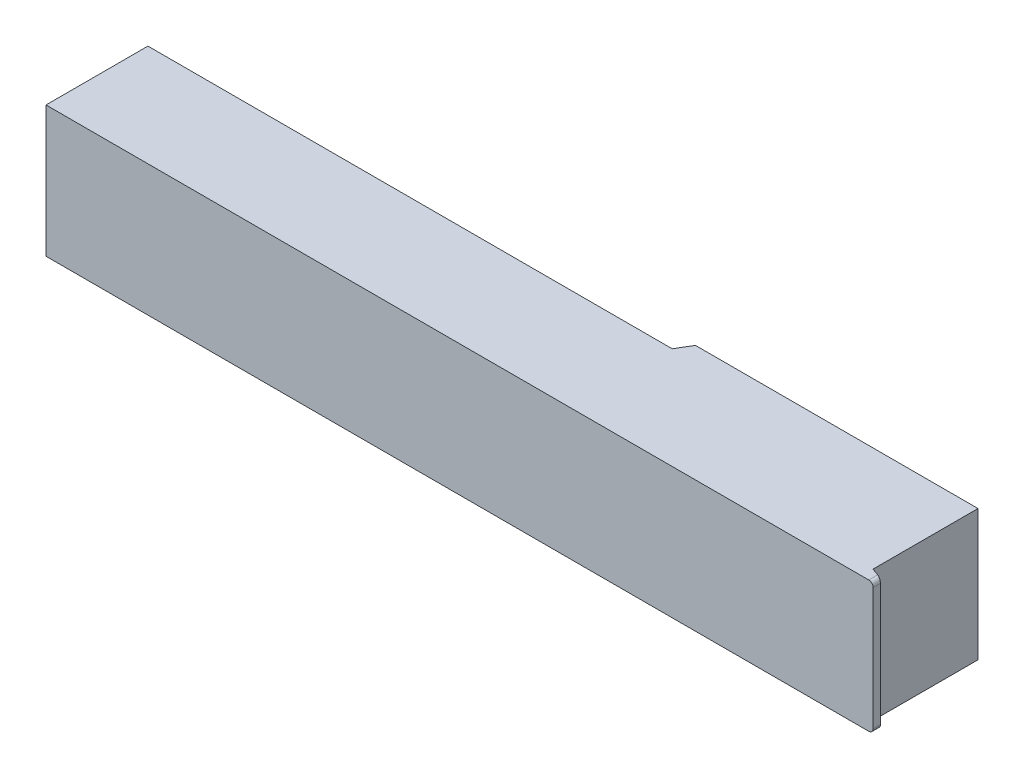
SolidWorks part; units mm, degrees
ref_plane "Front Plane" through (0, 0, 0) normal (1, 0, 0) x (0, 1, 0)
ref_plane "Top Plane" through (0, 0, 0) normal (0, 0, 1) x (0, 1, 0)
ref_plane "Right Plane" through (0, 0, 0) normal (0, 1, 0) x (-1, 0, 0)
sketch "Sketch1" plane through (0, 0, 0) normal (0, 0, 1) x (0, 1, 0)
  line L1 (0, 0) -> (22.5, 0)
  line L2 (0, 0) -> (0, -142)
  line L3 (0, -142) -> (22.5, -142)
  line L4 (22.5, 0) -> (22.5, -142)
extrude "Boss-Extrude1" add sketch "Sketch1" against normal blind 20 contours L2 L3 L4 L1
sketch "Sketch2" plane through (142, 0, 0) normal (1, 0, 0) x (0, 1, 0)
  line L0 (22.5, -20) -> (22.5, 0) construction
  line L1 (0, -20) -> (22.5, -20)
  line L2 (0, -20) -> (0, -2)
  line L3 (0, -2) -> (22.5, -2)
  line L4 (22.5, -20) -> (22.5, -2)
extrude "Cut-Extrude1" cut sketch "Sketch2" against normal blind 2 contours L3 L4 L1 L2
chamfer "Chamfer5" distance 0.75 angle 70 1 edges at (142, 11.25, -2)
fillet "Fillet5" radius 0.75 2 edges at (142, 0, -0.625) (142, 22.5, -0.625)
sketch "Sketch3" plane through (0, 22.5, 0) normal (0, 1, 0) x (-1, 0, 0)
  line L0 (0, 0) -> (-141.25, 0) construction
  line L1 (-140, -20) -> (-30, -20)
  line L2 (-140, -20) -> (-140, 0)
  line L3 (-140, 0) -> (-30, 0)
  line L4 (-30, -20) -> (-30, 0)
  line L5 (0, -20) -> (0, 0) construction
  line L6 (-30, -20) -> (0, -20)
  line L7 (-30, -20) -> (-30, -10)
  line L8 (-30, -10) -> (0, -10)
  line L9 (0, -20) -> (0, -10)
  line L11 (-30, 0) -> (0, 0)
  line L12 (-30, 0) -> (-30, -2.5)
  line L17 (-30, -2.5) -> (0, -2.5)
  line L18 (0, 0) -> (0, -2.5)
extrude "Cut-Extrude2" [suppressed] cut sketch "Sketch3" against normal up to surface (22.5 mm away) contours L12 L17 L18 L11
sketch3d "3DSketch1" plane through (0, 0, 0) normal (0, 0, 1) x (1, 0, 0)
  dimension "D1" = 11.25
sketch "Sketch4" plane through (0, 11.25, 0) normal (0, 1, 0) x (1, 0, 0)
  line L0 (30, 20) -> (165, 20)
  line L1 (140, 20) -> (30, 20) construction
  line L2 (165, 20) -> (165, 7.5)
  line L3 (165, 7.5) -> (30, 20)
  dimension "D1" = 12.5
  dimension "D2" = 135
sketch "Sketch5" plane through (0, 0, -20) normal (0, 0, -1) x (-1, 0, 0)
  line L0 (0, 22.5) -> (-140, 22.5) construction
  line L1 (-140, 0) -> (-91.5, 0)
  line L2 (-140, 0) -> (-140, 22.5)
  line L3 (-140, 22.5) -> (-91.5, 22.5)
  line L4 (-91.5, 0) -> (-91.5, 22.5)
  line L5 (-138, 2) -> (-93.5, 2)
  line L6 (-93.5, 2) -> (-93.5, 20.5)
  line L7 (-138, 20.5) -> (-93.5, 20.5)
  line L8 (-138, 2) -> (-138, 20.5)
  line L9 (-93.5, 20.5) -> (-91.5, 22.5)
  line L10 (-93.5, 2) -> (-91.5, 0)
  line L12 (-91.5, 22.5) -> (0, 22.5)
  line L13 (-91.5, 22.5) -> (-91.5, 0)
  line L14 (-91.5, 0) -> (0, 0)
  line L15 (0, 22.5) -> (0, 0)
  line M6 (-140, 0) -> (0, 0)
  line M7 (0, 0) -> (0, 22.5)
  line M8 (0, 22.5) -> (-140, 22.5)
  dimension "D1" = 2
extrude "Cut-Extrude3" [suppressed] cut sketch "Sketch5" against normal blind 7.5 contours L8 L5 L6 L7 | L6 L10 L4 L9 | L4 M6 M7 M8
sketch "Sketch6" plane through (0, 22.5, 0) normal (0, 1, 0) x (-1, 0, 0)
  line L0 (-90, -17.5) -> (-91.5, -20)
  line L1 (-140, -20) -> (-90, -20) construction
  line L2 (-140, -20) -> (-140, -17.5) construction
  line L3 (-140, -17.5) -> (-90, -17.5) construction
  line L4 (-90, -20) -> (-90, -17.5) construction
  line L5 (0, -20) -> (-140, -20) construction
  line L7 (-90, -17.5) -> (0, -17.5)
  line L8 (-90, -17.5) -> (-90, -20) construction
  line L9 (-90, -20) -> (0, -20)
  line L10 (0, -17.5) -> (0, -20)
extrude "Cut-Extrude4" cut sketch "Sketch6" against normal through all and the other way through all
